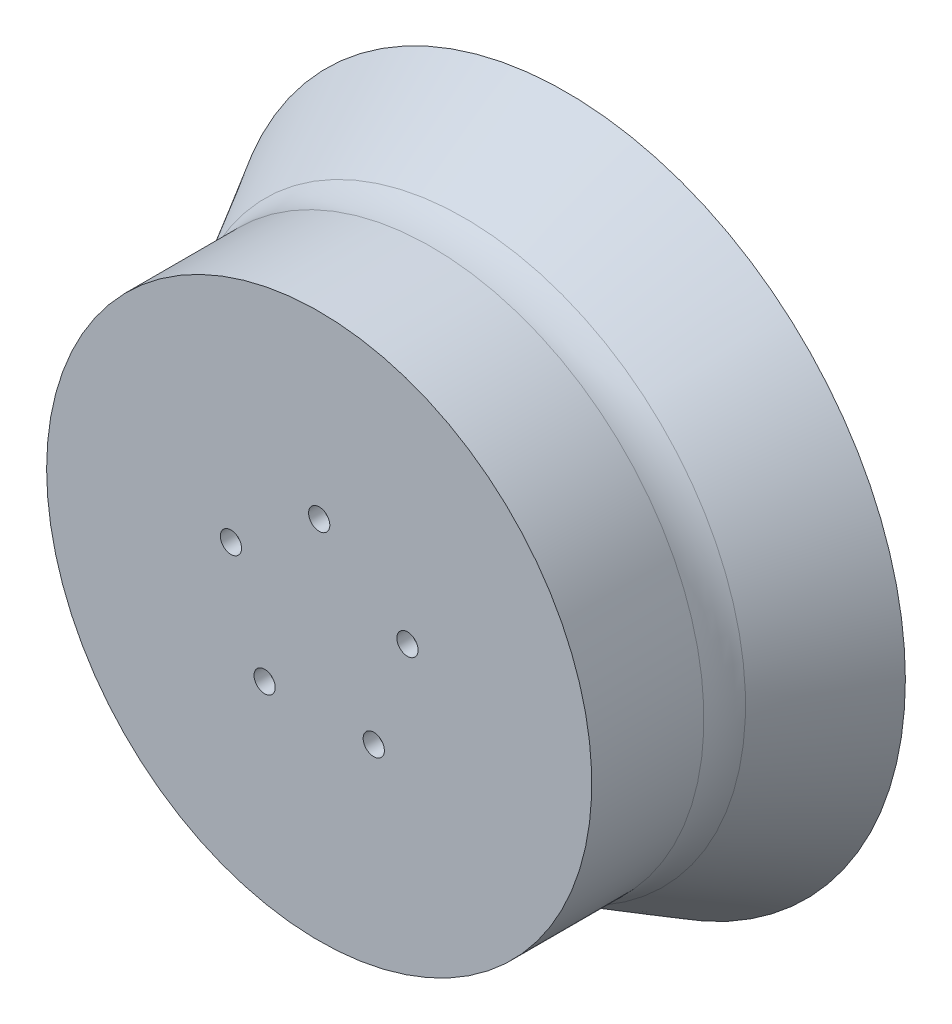
SolidWorks part; units mm, degrees
ref_plane "Front Plane" through (0, 0, 0) normal (0, 0, 1) x (1, 0, 0)
ref_plane "Top Plane" through (0, 0, 0) normal (0, 1, 0) x (1, 0, 0)
ref_plane "Right Plane" through (0, 0, 0) normal (1, 0, 0) x (0, 0, -1)
sketch "Sketch1" plane through (0, 0, 0) normal (0, 1, 0) x (1, 0, 0)
  line L0 (-44.45, -25.4) -> (44.45, -25.4) construction
  line L1 (7.7629, -25.4) -> (44.45, -25.4)
  line L2 (0, 0) -> (0, -35.687) construction
  line L3 (44.45, 0) -> (-44.45, 0) construction
  line L4 (44.45, -25.4) -> (44.45, 0)
  line L5 (44.45, -25.4) -> (44.45, 0) construction
  line L6 (0, -15.44) -> (0, -27.94)
  line L7 (0, -27.94) -> (46.99, -27.94)
  line L8 (46.99, -27.94) -> (46.99, -8.6126)
  line L9 (44.45, 0) -> (46.99, 0)
  line L10 (46.99, 0) -> (58.4734, 14.634)
  line L11 (58.4734, 14.634) -> (48.4889, -2.94)
  line L13 (7.9629, -25.4) -> (7.9629, -15.24) construction
  line L14 (7.9629, -25.4) -> (7.9629, -15.24) construction
  line L15 (7.9629, -15.24) -> (0, -15.24) construction
  line L16 (7.7629, -25.4) -> (7.7629, -17.44)
  line L17 (5.7629, -15.44) -> (0, -15.44)
  line L19 (5.7629, -15.44) -> (7.7629, -17.44)
  line L20 (7.7629, -15.44) -> (0, -15.44) construction
  line L21 (7.7629, -25.4) -> (7.7629, -15.44) construction
  arc A0 (46.99, -8.6126) -> (48.4889, -2.94) centre (58.4734, -8.6126) cw
  point P26 (5.7965, -15.44)
  dimension "D3" = 11.4834
  dimension "D7" = 45
  dimension "D1" = 2.54
  dimension "D2" = 2.54
  dimension "D4" = 2.94
  dimension "D5" = 0.2
  dimension "D6" = 12.7
  dimension "D8" = 2
revolve "Revolve1" add sketch "Sketch1" angle 360 about L2
sketch "Sketch2" plane through (0, 0, 27.94) normal (0, 0, 1) x (1, 0, 0)
  circle A0 centre (0, 16) radius 3.556
  circle A1 centre (0, 16) radius 1.8288
  circle A2 centre (0, 16) radius 1.8288
  circle A3 centre (15.2169, 4.9443) radius 1.8288
  circle A4 centre (15.2169, 4.9443) radius 1.8288
  circle A5 centre (9.4046, -12.9443) radius 1.8288
  circle A6 centre (9.4046, -12.9443) radius 1.8288
  circle A7 centre (-9.4046, -12.9443) radius 1.8288
  circle A8 centre (-9.4046, -12.9443) radius 1.8288
  circle A9 centre (-15.2169, 4.9443) radius 1.8288
  circle A10 centre (-15.2169, 4.9443) radius 1.8288
  circle A11 centre (15.2169, 4.9443) radius 3.556
  circle A12 centre (9.4046, -12.9443) radius 3.556
  circle A13 centre (-9.4046, -12.9443) radius 3.556
  circle A14 centre (-15.2169, 4.9443) radius 3.556
  dimension "D6" = 7.112
  dimension "D1" = 0
  dimension "D2" = 0
  dimension "D3" = 0
  dimension "D4" = 0
  dimension "D5" = 0
extrude "Cut-Extrude1" cut sketch "Sketch2" against normal through all contours A10 | A2 | A8 | A6 | A4
